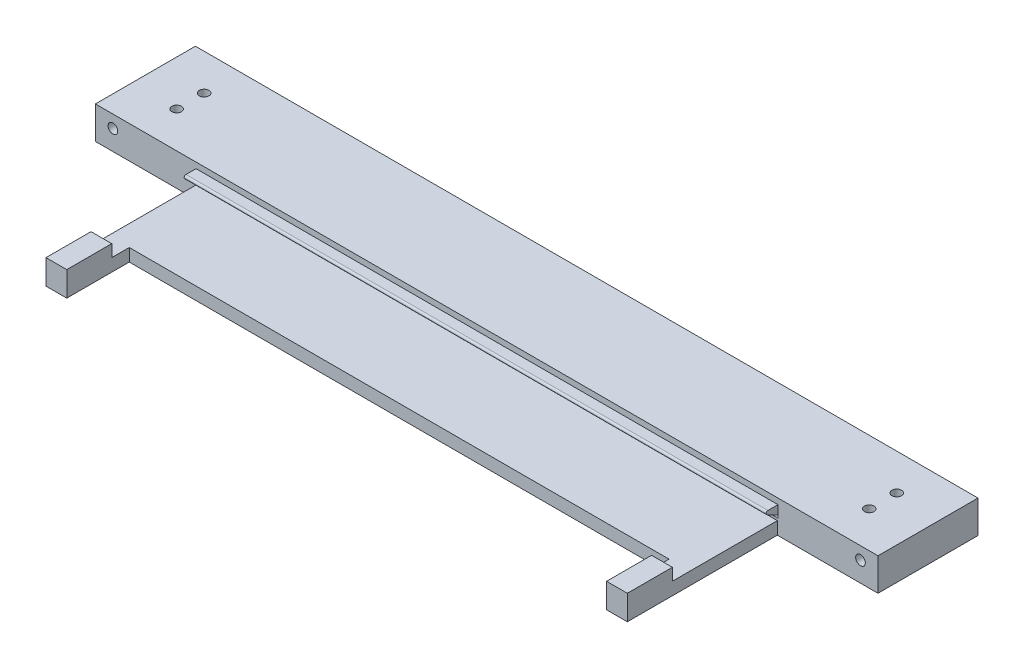
SolidWorks part; units mm, degrees
ref_plane "Front Plane" through (0, 0, 0) normal (0, 0, 1) x (1, 0, 0)
ref_plane "Top Plane" through (0, 0, 0) normal (0, 1, 0) x (1, 0, 0)
ref_plane "Right Plane" through (0, 0, 0) normal (1, 0, 0) x (0, 0, -1)
sketch "Sketch1" plane through (0, 0, 0) normal (1, 0, 0) x (0, 0, -1)
  line L1 (0, 0) -> (40, 0)
  line L2 (0, 0) -> (0, 10)
  line L3 (0, 10) -> (40, 10)
  line L4 (40, 0) -> (40, 10)
  dimension "D1" = 10
  dimension "D2" = 40
extrude "Boss-Extrude1" add sketch "Sketch1" along normal blind 312.998
sketch "Sketch2" plane through (0, 0, -40) normal (0, 0, -1) x (-1, 0, 0)
  line L1 (-272.994, 3) -> (-40.004, 3)
  line L2 (-272.994, 3) -> (-272.994, 4.2)
  line L3 (-272.994, 4.2) -> (-40.004, 4.2)
  line L4 (-40.004, 3) -> (-40.004, 4.2)
  line L5 (-272.994, 4.2) -> (-312.998, 0) construction
  line L6 (-40.004, 4.2) -> (0, 0) construction
  line L7 (-312.998, 0) -> (0, 0) construction
  dimension "D1" = 232.99
  dimension "D2" = 3
  dimension "D3" = 1.2
extrude "Cut-Extrude1" cut sketch "Sketch2" against normal through all
sketch "Sketch3" plane through (0, 10, 0) normal (0, 1, 0) x (1, 0, 0)
  line L0 (156.499, 71.4665) -> (156.499, -49.9307) construction
  line L1 (0, 40) -> (156.499, 71.4665) construction
  line L2 (156.499, 71.4665) -> (312.998, 40) construction
  line L3 (312.998, 40) -> (312.998, 0) construction
  line L4 (312.998, 40) -> (0, 40) construction
  line L5 (312.998, 40) -> (294.998, 25.5) construction
  line L6 (294.998, 25.5) -> (294.998, 14.5) construction
  line L7 (294.998, 14.5) -> (312.998, 0) construction
  circle A0 centre (294.998, 25.5) radius 1.9177
  circle A1 centre (294.998, 14.5) radius 1.9177
  circle A2 centre (18, 14.5) radius 1.9177
  circle A3 centre (18, 25.5) radius 1.9177
  dimension "D3" = 3.8354
  dimension "D1" = 18
  dimension "D2" = 14.5
extrude "Cut-Extrude2" cut sketch "Sketch3" against normal through all
sketch "Sketch4" plane through (0, 0, 0) normal (0, -1, 0) x (1, 0, 0)
  line L1 (14.5837, -12.5276) -> (14.5837, -16.4724)
  line L2 (14.5837, -16.4724) -> (18, -18.4448)
  line L3 (18, -18.4448) -> (21.4163, -16.4724)
  line L4 (21.4163, -16.4724) -> (21.4163, -12.5276)
  line L5 (21.4163, -12.5276) -> (18, -10.5552)
  line L6 (18, -10.5552) -> (14.5837, -12.5276)
  line L7 (14.5837, -23.5276) -> (14.5837, -27.4724)
  line L8 (14.5837, -27.4724) -> (18, -29.4448)
  line L9 (18, -29.4448) -> (21.4163, -27.4724)
  line L10 (21.4163, -27.4724) -> (21.4163, -23.5276)
  line L11 (21.4163, -23.5276) -> (18, -21.5552)
  line L12 (18, -21.5552) -> (14.5837, -23.5276)
  line L13 (298.4143, -12.5276) -> (294.998, -10.5552)
  line L14 (294.998, -10.5552) -> (291.5817, -12.5276)
  line L15 (291.5817, -12.5276) -> (291.5817, -16.4724)
  line L16 (291.5817, -16.4724) -> (294.998, -18.4448)
  line L17 (294.998, -18.4448) -> (298.4143, -16.4724)
  line L18 (298.4143, -16.4724) -> (298.4143, -12.5276)
  line L19 (291.5817, -23.5276) -> (291.5817, -27.4724)
  line L20 (291.5817, -27.4724) -> (294.998, -29.4448)
  line L21 (294.998, -29.4448) -> (298.4143, -27.4724)
  line L22 (298.4143, -27.4724) -> (298.4143, -23.5276)
  line L23 (298.4143, -23.5276) -> (294.998, -21.5552)
  line L24 (294.998, -21.5552) -> (291.5817, -23.5276)
  circle A0 centre (18, -14.5) radius 3.4163 construction
  circle A1 centre (18, -25.5) radius 3.4163 construction
  circle A2 centre (294.998, -14.5) radius 3.4163 construction
  circle A3 centre (294.998, -25.5) radius 3.4163 construction
  dimension "D1" = 6.8326
extrude "Cut-Extrude3" cut sketch "Sketch4" against normal blind 4.3
sketch "Sketch5" plane through (0, 0, 0) normal (0, 0, 1) x (1, 0, 0)
  line L0 (0, 10) -> (7, 5) construction
  line L1 (7, 5) -> (0, 0) construction
  line L2 (0, 10) -> (156.499, 87.0064) construction
  line L3 (156.499, 87.0064) -> (312.998, 10) construction
  line L4 (312.998, 10) -> (312.998, 0) construction
  line L5 (312.998, 10) -> (0, 10) construction
  line L6 (156.499, 87.0064) -> (156.499, -80.9825) construction
  line L7 (305.998, 5) -> (312.998, 0) construction
  line L8 (312.998, 10) -> (305.998, 5) construction
  circle A0 centre (7, 5) radius 1.9304
  circle A1 centre (305.998, 5) radius 1.9304
  dimension "D1" = 3.8608
  dimension "D2" = 7
extrude "Cut-Extrude4" cut sketch "Sketch5" against normal through all
sketch "Sketch6" plane through (0, 0, 0) normal (-1, 0, 0) x (0, 0, 1)
  line L0 (-40, 10) -> (-33, 8.4163) construction
  line L1 (-33, 8.4163) -> (-29.8453, 8.4163)
  line L2 (-33, 8.4163) -> (-33, 1.5837)
  line L3 (-33, 1.5837) -> (-29.8453, 1.5837)
  line L4 (-29.8453, 8.4163) -> (-29.8453, 1.5837)
  line L9 (-33, 1.5837) -> (-40, 0) construction
  line L10 (-40, 10) -> (-20, 18.9404) construction
  line L11 (-20, 18.9404) -> (0, 10) construction
  line L12 (-20, 18.9404) -> (-20, -7.3414) construction
  line L13 (-7, 1.5837) -> (0, 0) construction
  line L14 (0, 10) -> (-7, 8.4163) construction
  line L15 (-10.1547, 8.4163) -> (-10.1547, 1.5837)
  line L16 (-7, 1.5837) -> (-10.1547, 1.5837)
  line L17 (-7, 8.4163) -> (-7, 1.5837)
  line L18 (-7, 8.4163) -> (-10.1547, 8.4163)
  dimension "D1" = 7
  dimension "D2" = 3.1547
  dimension "D3" = 6.8326
extrude "Cut-Extrude5" cut sketch "Sketch6" against normal blind 15
ref_plane "Plane1" through (156.499, 0, 0) normal (-1, 0, 0) x (0, 0, 1)
sketch "Sketch7" plane through (0, 0, 0) normal (0, 0, 1) x (1, 0, 0)
  line L0 (312.998, 0) -> (0, 0) construction
  line L1 (40.249, 0) -> (272.749, 0)
  line L2 (40.249, 0) -> (40.249, 2.0463)
  line L3 (40.249, 2.0463) -> (272.749, 2.0463)
  line L4 (272.749, 0) -> (272.749, 2.0463)
  line L5 (40.249, 2.0463) -> (40.004, 4.2) construction
  line L6 (272.994, 4.2) -> (272.749, 2.0463) construction
  dimension "D1" = 232.5
extrude "Boss-Extrude2" add sketch "Sketch7" along normal blind 60
sketch "Sketch8" plane through (0, 2.0463, 0) normal (0, 1, 0) x (1, 0, 0)
  line L0 (272.749, -60) -> (40.249, -60) construction
  line L1 (48.549, -35) -> (264.449, -35)
  line L2 (48.549, -35) -> (48.549, -60)
  line L3 (48.549, -60) -> (264.449, -60)
  line L4 (264.449, -35) -> (264.449, -60)
  line L5 (48.549, -35) -> (40.249, -60) construction
  line L6 (272.749, -60) -> (264.449, -35) construction
  dimension "D1" = 25
  dimension "D2" = 215.9
extrude "Cut-Extrude6" cut sketch "Sketch8" against normal up to next
sketch "Sketch9" plane through (0, 0, 0) normal (0, -1, 0) x (1, 0, 0)
  line L0 (0, -40) -> (0, 0)
  line L1 (0, 0) -> (40.249, 0)
  line L2 (40.249, 0) -> (40.249, 60)
  line L3 (40.249, 60) -> (48.549, 60)
  line L4 (48.549, 60) -> (48.549, 35)
  line L5 (48.549, 35) -> (264.449, 35)
  line L6 (264.449, 35) -> (264.449, 60)
  line L7 (264.449, 60) -> (272.749, 60)
  line L8 (272.749, 60) -> (272.749, 0)
  line L9 (272.749, 0) -> (312.998, 0)
  line L10 (312.998, 0) -> (312.998, -40)
  line L11 (312.998, -40) -> (0, -40)
  line L12 (21.4163, -16.4724) -> (21.4163, -12.5276) construction
  line L13 (17.9977, -10.5552) -> (14.5825, -12.5296)
  line L14 (14.5825, -12.5296) -> (14.5849, -16.4744)
  line L15 (14.5849, -16.4744) -> (18.0023, -18.4448)
  line L16 (18.0023, -18.4448) -> (21.4175, -16.4704)
  line L17 (21.4175, -16.4704) -> (21.4151, -12.5256)
  line L18 (21.4151, -12.5256) -> (17.9977, -10.5552)
  line L19 (18.0023, -21.5552) -> (14.5849, -23.5256)
  line L20 (14.5849, -23.5256) -> (14.5825, -27.4704)
  line L21 (14.5825, -27.4704) -> (17.9977, -29.4448)
  line L22 (17.9977, -29.4448) -> (21.4151, -27.4744)
  line L23 (21.4151, -27.4744) -> (21.4175, -23.5296)
  line L24 (21.4175, -23.5296) -> (18.0023, -21.5552)
  line L25 (295.0003, -10.5552) -> (291.5828, -12.5256)
  line L26 (291.5828, -12.5256) -> (291.5805, -16.4704)
  line L27 (291.5805, -16.4704) -> (294.9956, -18.4448)
  line L28 (294.9956, -18.4448) -> (298.4131, -16.4744)
  line L29 (298.4131, -16.4744) -> (298.4154, -12.5296)
  line L30 (298.4154, -12.5296) -> (295.0003, -10.5552)
  line L31 (294.9956, -21.5552) -> (291.5805, -23.5296)
  line L32 (291.5805, -23.5296) -> (291.5828, -27.4744)
  line L33 (291.5828, -27.4744) -> (295.0003, -29.4448)
  line L34 (295.0003, -29.4448) -> (298.4154, -27.4704)
  line L35 (298.4154, -27.4704) -> (298.4131, -23.5256)
  line L36 (298.4131, -23.5256) -> (294.9956, -21.5552)
  circle A0 centre (18, -14.5) radius 3.4163 construction
  circle A1 centre (18, -25.5) radius 3.4163 construction
  circle A2 centre (294.998, -14.5) radius 3.4163 construction
  circle A3 centre (294.998, -25.5) radius 3.4163 construction
extrude "Boss-Extrude3" add sketch "Sketch9" along normal blind 3
sketch "Sketch10" plane through (40.249, 0, 0) normal (-1, 0, 0) x (0, 0, 1)
  line L1 (60, 2.0463) -> (42, 2.0463)
  line L2 (60, 2.0463) -> (60, 6.8906)
  line L3 (60, 6.8906) -> (42, 6.8906)
  line L4 (42, 2.0463) -> (42, 6.8906)
  dimension "D1" = 18
extrude "Boss-Extrude4" add sketch "Sketch10" against normal up to surface (8.3 mm away) up to face at (48.549, -0.4768, 47.5)
sketch "Sketch12" plane through (40.249, 0, 0) normal (-1, 0, 0) x (0, 0, 1)
  line L4 (0, 4.2) -> (7, 7.7)
  line L5 (7, 7.7) -> (0, 7.7)
  line L6 (0, 7.7) -> (0, 4.2)
  line L7 (0, 10) -> (0, -3) construction
  dimension "D1" = 7
  dimension "D2" = 3.5
extrude "Boss-Extrude6" add sketch "Sketch12" against normal up to surface (232.745 mm away) up to face at (272.994, 3.6, -20)
fillet "Fillet1" radius 0.7 1 edges at (156.6215, 7.7, 7)
sketch "Sketch15" plane through (0, 2.0463, 0) normal (0, 1, 0) x (1, 0, 0)
  line L1 (264.449, -42) -> (272.749, -42)
  line L2 (264.449, -42) -> (264.449, -60)
  line L3 (264.449, -60) -> (272.749, -60)
  line L4 (272.749, -42) -> (272.749, -60)
  dimension "D1" = 18
extrude "Boss-Extrude8" add sketch "Sketch15" along normal up to surface (4.8443 mm away) up to face at (44.399, 6.8906, 51)
